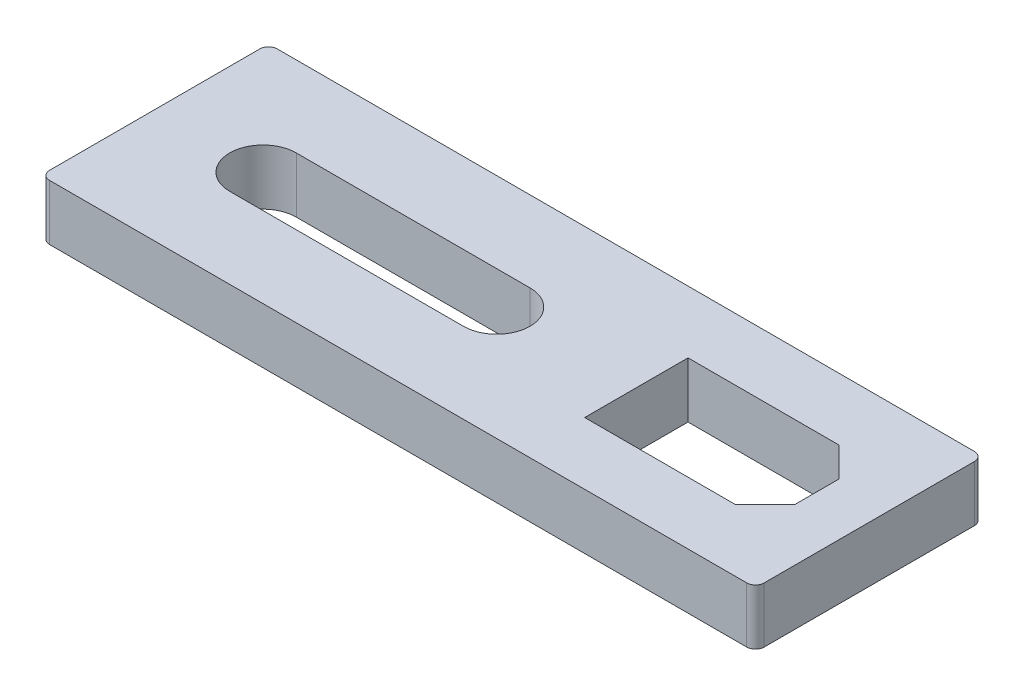
SolidWorks part; units mm, degrees
ref_plane "Front Plane" through (0, 0, 0) normal (0, 0, 1) x (1, 0, 0)
ref_plane "Top Plane" through (0, 0, 0) normal (0, 1, 0) x (1, 0, 0)
ref_plane "Right Plane" through (0, 0, 0) normal (1, 0, 0) x (0, 0, -1)
sketch "Sketch1" plane through (0, 0, 0) normal (0, 1, 0) x (1, 0, 0)
  line L0 (0, 6.5) -> (40.8, 6.5) construction
  line L1 (0, 0) -> (40.8, 0)
  line L2 (0, 0) -> (0, 13)
  line L3 (0, 13) -> (40.8, 13)
  line L4 (40.8, 0) -> (40.8, 13)
  line L5 (25, 13) -> (25, 0) construction
  line L6 (37.75, 7.75) -> (36.1, 9.4) construction
  line L7 (27.55, 3.6) -> (36.1, 3.6) construction
  line L8 (27.55, 3.6) -> (27.55, 9.4) construction
  line L9 (27.55, 9.4) -> (36.1, 9.4) construction
  line L10 (37.75, 5.25) -> (37.75, 7.75) construction
  line L12 (27.55, 6.5) -> (27.2, 6.5) construction
  line L13 (37.75, 5.25) -> (36.1, 3.6) construction
  line L14 (37.8, 5.2293) -> (37.8, 7.7707)
  line L15 (37.8, 7.7707) -> (36.1207, 9.45)
  line L16 (27.5, 9.45) -> (36.1207, 9.45)
  line L17 (27.5, 3.55) -> (27.5, 9.45)
  line L18 (27.5, 3.55) -> (36.1207, 3.55)
  line L19 (37.8, 5.2293) -> (36.1207, 3.55)
  line L20 (6.1834, 6.5) -> (19.5276, 6.5) construction
  line L21 (6.1834, 8.4) -> (19.5276, 8.4)
  line L22 (6.1834, 4.6) -> (19.5276, 4.6)
  arc A1 (6.1834, 8.4) -> (6.1834, 4.6) centre (6.1834, 6.5) ccw
  arc A2 (19.5276, 4.6) -> (19.5276, 8.4) centre (19.5276, 6.5) ccw
  point P11 (21.9379, 6.5)
  point P12 (37.75, 6.5)
  point P19 (12.8555, 6.5)
  dimension "D2" = 1.9
  dimension "D1" = 13
  dimension "D4" = 25
  dimension "D5" = 10.2
  dimension "D6" = 5.8
  dimension "D7" = 2.5
  dimension "D8" = 135
  dimension "D10" = 2.5
  dimension "D11" = 3
  dimension "D9" = 0.05
extrude "Boss-Extrude1" add sketch "Sketch1" along normal blind 3.175
fillet "Fillet1" radius 0.5 4 edges at (40.8, 1.5875, -13) (40.8, 1.5875, 0) (0, 1.5875, -13) (0, 1.5875, 0)
